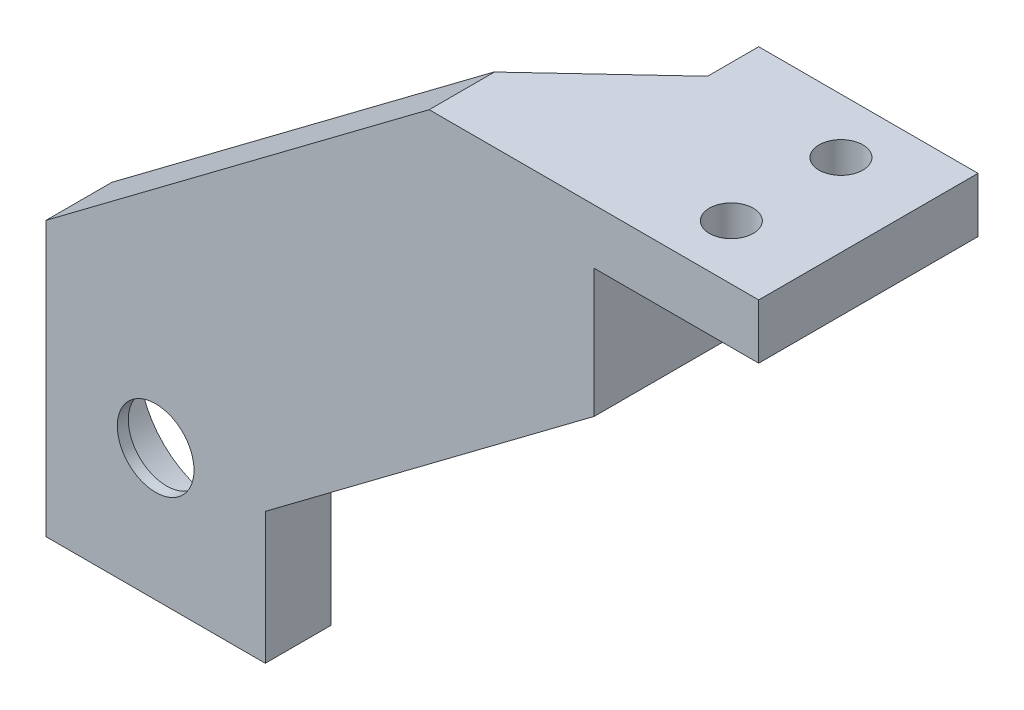
SolidWorks part; units mm, degrees
ref_plane "Front Plane" through (0, 0, 0) normal (0, 0, 1) x (1, 0, 0)
ref_plane "Top Plane" through (0, 0, 0) normal (0, 1, 0) x (1, 0, 0)
ref_plane "Right Plane" through (0, 0, 0) normal (1, 0, 0) x (0, 0, -1)
sketch "Sketch1" plane through (0, 0, 0) normal (0, 0, 1) x (1, 0, 0)
  circle A0 centre (0, 0) radius 7.5
  circle A1 centre (0, 0) radius 3.5
  circle A2 centre (0, 0) radius 10
  dimension "D1" = 15
  dimension "D2" = 20
  dimension "D3" = 7
extrude "Boss-Extrude1" add sketch "Sketch1" against normal up to surface (5 mm away) contours A2 A0 region at (-9.7172, 0, 0)
extrude "Boss-Extrude2" add sketch "Sketch1<3>" along normal blind 1 contours A0 A1 | A2 A0 region at (-7.2879, 0, 0) region at (-9.7172, 0, 0)
sketch "Sketch1<3>" plane through (0, 0, 0) normal (0, 0, 1) x (1, 0, 0) same geometry as "Sketch1"
sketch "Sketch2" plane through (0, 0, 1) normal (0, 0, 1) x (1, 0, 0)
  line L0 (10, 0) -> (40, 22.5)
  line L1 (40, 22.5) -> (40, 34.2)
  line L2 (40, 34.2) -> (-10, 34.2)
  line L3 (290, 34.2) -> (-110, 34.2) construction
  line L4 (-10, 34.2) -> (-10, 0)
  line L5 (-10, 0) -> (-10, -12)
  line L6 (-10, -12) -> (10, -12)
  line L7 (10, -12) -> (10, 0)
  line L9 (-10, 34.2) -> (55, 34.2)
  line L10 (-10, 34.2) -> (-10, 39.2)
  line L11 (-10, 39.2) -> (55, 39.2)
  line L12 (55, 34.2) -> (55, 39.2)
  line L13 (-10, 34.2) -> (55, 39.2) construction
  line L14 (-10, 39.2) -> (55, 34.2) construction
  circle A0 centre (0, 0) radius 10 construction
  circle A1 centre (0, 0) radius 10
  point P20 (22.5, 36.7)
  circle M4 centre (0, 0) radius 10
  dimension "D1" = 12
  dimension "D2" = 20
  dimension "D3" = 5
  dimension "D4" = 15
extrude "Boss-Extrude3" add sketch "Sketch2" against normal up to surface (6 mm away) contours L2 L4 L0 L1 M4 | L6 L7 L5 M4 | L9 L12 L11 L10 L2 region at (12.7734, 21.4272, 1) region at (9.7668, -6, 1) region at (22.5, 36.7, 1) up to face at (-10, 0, -5)
sketch "Sketch3" plane through (0, 39.2, 0) normal (0, 1, 0) x (1, 0, 0)
  line L0 (55, -1) -> (55, 19)
  line L1 (55, 19) -> (40, 19)
  line L2 (40, 19) -> (40, 5)
  line L3 (-10, 5) -> (55, 5) construction
  line L4 (40, 286) -> (40, -14) construction
  line L5 (-10, -1) -> (55, -1) construction
  line L6 (40, 19) -> (35, 19)
  line L7 (35, 19) -> (35, 5)
  line M4 (55, 5) -> (-10, 5)
  dimension "D1" = 20
  dimension "D2" = 5
extrude "Boss-Extrude4" add sketch "Sketch3" against normal up to surface (5 mm away) contours L1 L2 L0 M4 | L6 L7 L2 M4 region at (47.5, 39.2, -12) region at (37.5, 39.2, -12)
sketch "Sketch4" plane through (0, 39.2, 0) normal (0, 1, 0) x (1, 0, 0)
  line L0 (40, 19) -> (25, 5)
  line L1 (-10, 5) -> (35, 5) construction
  line L3 (55, 19) -> (35, 19) construction
  line L4 (40, 286) -> (40, -14) construction
  line L5 (40, 19) -> (40, -1)
  line L6 (-10, -1) -> (55, -1) construction
  line L7 (40, -1) -> (25, -1)
  line L8 (25, -1) -> (25, 5)
  point P15 (25, 4.9031)
  dimension "D1" = 10
extrude "Boss-Extrude6" add sketch "Sketch4" against normal up to surface (16.7 mm away) up to face at (25, 11.25, -2)
extrude "Boss-Extrude5" add sketch "Sketch3<3>" against normal up to surface (16.7 mm away) contours L6 L7 L2 M4 region at (37.5, 39.2, -12) up to face at (25, 11.25, -5.4)
sketch "Sketch3<3>" plane through (0, 39.2, 0) normal (0, 1, 0) x (1, 0, 0) same geometry as "Sketch3"
sketch "Sketch5" plane through (0, 39.2, 0) normal (0, 1, 0) x (1, 0, 0)
  line L0 (55, 19) -> (35, 19) construction
  line L1 (55, -1) -> (40, -1) construction
  line L2 (55, -1) -> (55, 19) construction
  line L3 (55, 19) -> (40, 19) construction
  line L4 (40, -1) -> (40, 19) construction
  line L5 (55, -1) -> (40, 19) construction
  line L6 (55, 19) -> (40, -1) construction
  line L7 (40, 286) -> (40, -14) construction
  line L8 (40, 9) -> (55, 9) construction
  circle A0 centre (47.5, 14) radius 2
  circle A1 centre (47.5, 14) radius 4 construction
  circle A2 centre (47.5, 4) radius 4 construction
  circle A3 centre (47.5, 4) radius 2
  point P4 (47.5, 9)
  dimension "D1" = 8
  dimension "D2" = 4
  dimension "D3" = 5
  dimension "D4" = 7.5
extrude "Cut-Extrude1" cut sketch "Sketch5" against normal through all
sketch "Sketch6" plane through (0, 0, 1) normal (0, 0, 1) x (1, 0, 0)
  line L0 (0, 20.4884) -> (24.9488, 39.2)
  line L2 (10, 0) -> (40, 22.5) construction
  line L3 (0, 20.4884) -> (-10, 12.9884)
  line L5 (24.9488, 39.2) -> (-10, 12.9884) construction
  line L6 (-10, 39.2) -> (-10, -12) construction
  line L7 (-10, 39.2) -> (55, 39.2) construction
  line L8 (-10, 12.9884) -> (-10, 39.2)
  line L9 (-10, 39.2) -> (24.9488, 39.2)
  dimension "D1" = 0
  dimension "D2" = 0
extrude "Cut-Extrude2" cut sketch "Sketch6" against normal through all both and the other way through all
